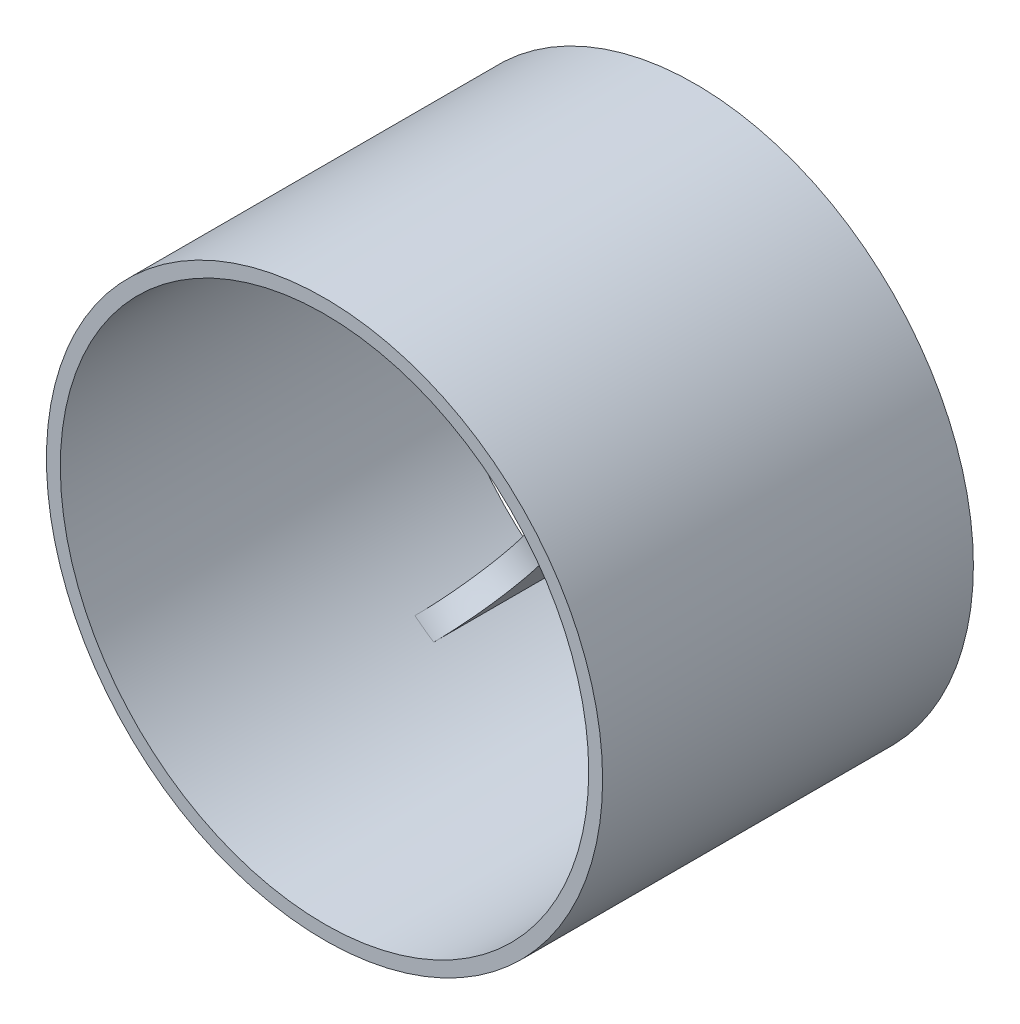
SolidWorks part; units mm, degrees
ref_plane "Front Plane" through (0, 0, 0) normal (0, 0, 1) x (1, 0, 0)
ref_plane "Top Plane" through (0, 0, 0) normal (0, 1, 0) x (1, 0, 0)
ref_plane "Right Plane" through (0, 0, 0) normal (1, 0, 0) x (0, 0, -1)
sketch "Sketch1" plane through (0, 0, 0) normal (0, 0, 1) x (1, 0, 0)
  line L0 (0, 60) -> (0, -60) construction
  line L1 (-60, 0) -> (60, 0) construction
  line L2 (-2.5, 56.9451) -> (-2.5, 9.6825)
  line L3 (2.5, 56.9451) -> (2.5, 9.6825) construction
  line L4 (-2.5, 60) -> (-2.5, -60) construction
  line L5 (2.5, 60) -> (2.5, -60) construction
  line L6 (53.3855, 19.9747) -> (8.436, 5.3697) [skipped]
  line L7 (54.9306, 15.2194) -> (9.9811, 0.6144) [skipped]
  line L8 (35.4941, -44.6001) -> (7.7137, -6.3638) [skipped]
  line L9 (31.449, -47.5391) -> (3.6687, -9.3027) [skipped]
  line L10 (-31.449, -47.5391) -> (-3.6687, -9.3027) [skipped]
  line L11 (-35.4941, -44.6001) -> (-7.7137, -6.3638) [skipped]
  line L12 (-54.9306, 15.2194) -> (-9.9811, 0.6144) construction
  line L13 (-53.3855, 19.9747) -> (-8.436, 5.3697)
  circle A0 centre (0, 0) radius 60
  circle A1 centre (0, 0) radius 2.5
  circle A2 centre (0, 0) radius 57 construction
  circle A3 centre (0, 0) radius 10 construction
  arc A4 (-2.5, 56.9451) -> (-53.3855, 19.9747) centre (0, 0) ccw
  arc A5 (-2.5, 9.6825) -> (-8.436, 5.3697) centre (0, 0) ccw
  point P22 (0, 0)
  point P38 (0, 0)
  point P40 (0, 0)
  dimension "D1" = 5
  dimension "D2" = 120
  dimension "D3" = 3
  dimension "D7" = 20
  dimension "D4" = 5
  dimension "D6" = 5
  dimension "D5" = 2.5
extrude "Boss-Extrude1" add sketch "Sketch1" along normal blind 80 contours A0
extrude "Cut-Extrude1" cut sketch "Sketch1<3>" along normal blind 80 contours L13 A5 L2 A4
sketch "Sketch1<3>" plane through (0, 0, 0) normal (0, 0, 1) x (1, 0, 0) same geometry as "Sketch1"
pattern_circular "CirPattern1" count 5 over 360 about axis through (0, 0, 80) along (0, 0, -1) of "Cut-Extrude1"
sketch "Sketch2" plane through (0, 0, 0) normal (1, 0, 0) x (0, 0, -1)
  line L0 (0, -60) -> (-80, -60)
  line L1 (-80, 60) -> (0, 60)
  line L2 (-80, 60) -> (0, 60)
  line L3 (0, -60) -> (-80, -60)
  line L4 (0, 0) -> (-80, 0)
  line L5 (0, 10) -> (-80, 10)
  line L6 (-10, 10) -> (-10, 0)
  line L7 (-10, 10) -> (-10, 42)
  line L8 (-80, 57) -> (-80, 0)
  line L9 (-25, 57) -> (-80, 57)
  line L10 (-10, 0) -> (-80, 0)
  line L11 (-80, -60) -> (-80, 60)
  arc A0 (-10, 42) -> (-25, 57) centre (-25, 42) ccw
  dimension "D3" = 15
  dimension "D2" = 10
  dimension "D4" = 3
  dimension "D1" = 10
revolve "Cut-Revolve1" cut sketch "Sketch2" angle 360 about L4 region at (0, 5, 45) region at (0, 33.1999, 45.4714)
hole_wizard "Ø5.0mm Dowel Hole1" positions "Sketch9" profile "Sketch10" hole size "Ø5.0" standard "ISO"
sketch "Sketch9" plane through (0, 0, 0) normal (0, 0, -1) x (-1, 0, 0)
  point P0 (0, 0)
sketch "Sketch10" plane through (0, 0, 0) normal (1, 0, 0) x (0, 1, 0)
  line L0 (0, 0) -> (0, 11.5022)
  line L1 (0, 11.5022) -> (2.5, 10)
  line L2 (2.5, 10) -> (2.5, 0)
  line L5 (2.5, 0) -> (0, 0)
  line L10 (0, 11.5022) -> (-2.5, 10) construction
  line L11 (0, -6.35) -> (0, 107.95) construction
  dimension "Hole Dia." = 5
  dimension "Hole Depth" = 10
  dimension "Drill Angle" = 118
equation "\"Wheel_Width\"= 80mm"
equation "\"D1@Cut-Extrude1\"=\"Wheel_Width\""
equation "\"Centre_Hole_Dia\"= 5mm"
equation "\"Internal_Spoke_Radius\"= 15mm"
equation "\"D3@Sketch2\"= \"Internal_Spoke_Radius\""
equation "\"Spoke_Thickness\"= 5mm"
equation "\"Hub_Depth\"= 10mm"
equation "\"D2@Sketch2\" = \"Hub_Depth\""
equation "\"Rim_Thickness\"= 3mm"
equation "\"D4@Sketch2\"=\"Rim_Thickness\""
equation "\"Hub_Radius\"= 10mm"
equation "\"D1@Sketch2\" = \"Hub_Radius\""
equation "\"D1@Sketch1\" = \"Centre_Hole_Dia\""
equation "\"D5@Sketch1\"=\"Spoke_Thickness\"/2"
equation "\"Wheel_Dia\"= 120mm"
equation "\"D2@Sketch1\" = \"Wheel_Dia\""
equation "\"D3@Sketch1\"=\"Rim_Thickness\""
equation "\"D4@Sketch1\"=\"Spoke_Thickness\""
equation "\"D7@Sketch1\"=\"Hub_Radius\"*2"
equation "\"Num_Spokes\"= 5"
equation "\"D6@Sketch1\"= \"Num_Spokes\""
equation "\"D1@CirPattern1\"=\"Num_Spokes\""
equation "\"Tread_Depth\"= 2mm"
